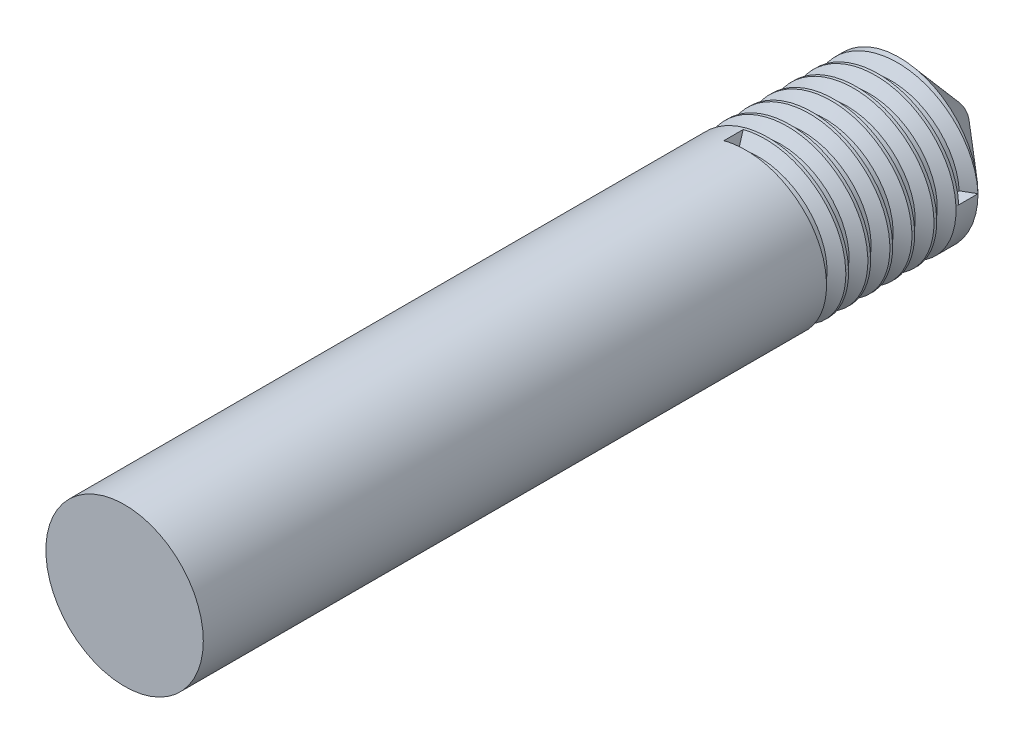
SolidWorks part; units mm, degrees
ref_plane "Front Plane" through (0, 0, 0) normal (0, 0, 1) x (1, 0, 0)
ref_plane "Top Plane" through (0, 0, 0) normal (0, 1, 0) x (1, 0, 0)
ref_plane "Right Plane" through (0, 0, 0) normal (1, 0, 0) x (0, 0, -1)
sketch "Sketch1" plane through (0, 0, 0) normal (0, 0, 1) x (1, 0, 0)
  circle A0 centre (0, 0) radius 1.25
  dimension "Diametru" = 2.5
extrude "Boss-Extrude1" add sketch "Sketch1" along normal blind 12.3
sketch "Sketch2" plane through (0, 0, 0) normal (1, 0, 0) x (0, 0, -1)
  line L0 (0, 0) -> (0.9745, 0)
  line L1 (0, -1.25) -> (0, 1.25) construction
  line L2 (0.9151, 0.1944) -> (0, 1.25)
  line L3 (0.9745, -0.0813) -> (0.9745, 0.0813) construction
  line L4 (0, 0) -> (0, 1.25)
  line L5 (0, 1.25) -> (0, 0)
  spline S0 degree 2 poles (0.9151, 0.1944) (0.9745, 0.1259) (0.9745, 0) knots 0 0 0 1 1 1
revolve "Revolve1" add sketch "Sketch2" angle 360 about L0 region at (0, 0.4211, -0.3534)
thread "Thread1" pitch 0.35 method cut profile "Thread Profile1" parameters start angle 0, offset 0, "Lungime Filet"=2.2, pitch 0.35, diameter 2.5
ref_plane "Plane1" through (1.25, 0, 0) normal (0, -1, 0) x (1, 0, 0)
sketch "Thread Profile1" plane through (1.25, 0, 0) normal (0, -1, 0) x (1, 0, 0)
  line L0 (0, 0) -> (0, 0.35) construction
  line L11 (0, 0) -> (0, 0.3062)
  line L12 (0, 0.3062) -> (-0.1894, 0.1969)
  line L13 (-0.1894, 0.1969) -> (-0.1894, 0.1094)
  line L15 (-0.1894, 0.1094) -> (0, 0)
  line L17 (-0.1894, 0.1531) -> (0, 0.1531) construction
  point P2 (0, 0)
  dimension "Pitch" = 0.35
  dimension "Profile_Angle" = 60
  dimension "Profile_Land" = 0.0875
  dimension "Profile_Height" = 0.1894
